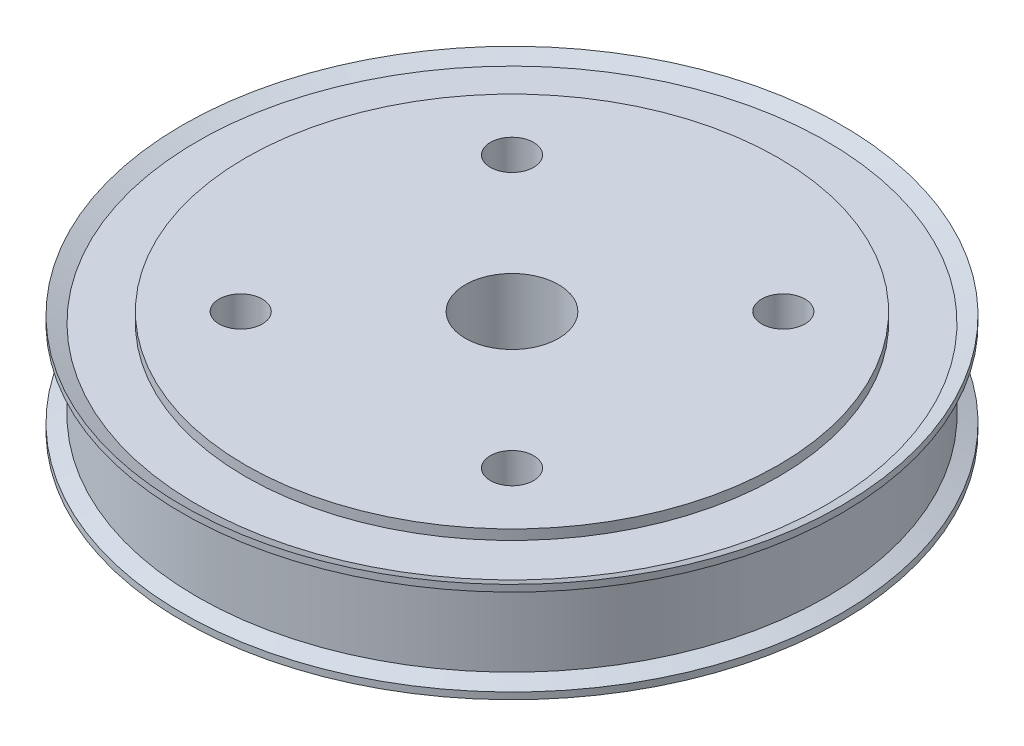
SolidWorks part; units mm, degrees
material "6061 合金"
ref_plane "前基準面" through (0, 0, 0) normal (0, 0, 1) x (1, 0, 0)
ref_plane "上基準面" through (0, 0, 0) normal (0, 1, 0) x (1, 0, 0)
ref_plane "右基準面" through (0, 0, 0) normal (1, 0, 0) x (0, 0, -1)
sketch "草圖1" plane through (0, 0, 0) normal (0, 0, 1) x (1, 0, 0)
  line L0 (0, 49.34) -> (0, -26.8952) construction
  line L1 (47.265, 0) -> (6.3419, 0) construction
  line L3 (7, -8) -> (7, 8)
  line L5 (47.265, 5.5) -> (40, 5.5)
  line L6 (40, 8) -> (40, 5.5)
  line L8 (47.745, 5.5) -> (47.745, -5.5) construction
  line L9 (47.265, -5.5) -> (47.265, 5.5)
  line L10 (40, -5.5) -> (47.265, -5.5)
  line L11 (40, 8) -> (7, 8)
  line L12 (40, -8) -> (40, -5.5)
  line L20 (40, -8) -> (7, -8)
  dimension "D2" = 14
  dimension "D3" = 94.53
  dimension "D6" = 11
  dimension "D7" = 80
  dimension "D8" = 16
  dimension "D9" = 33
  dimension "D12" = 95.49
  dimension "D15" = 7.265
revolve "旋轉1" add sketch "草圖1" angle 360 about L0
sketch "草圖7" plane through (0, 0, 0) normal (0, 0, 1) x (1, 0, 0)
  line L0 (0, 0) -> (0, 8) construction
  line L1 (40, 8) -> (-40, 8) construction
  line L3 (-47.265, -5.5) -> (47.265, -5.5) construction
  line L5 (-40, -5.5) -> (-40, -8) construction
  line L8 (0, 0) -> (-16, 0) construction
  line L12 (-49.5, -6.5) -> (-47.265, -5.5)
  line L13 (-49.5, -7.5) -> (-49.5, -6.5)
  line L14 (-49.5, -7.5) -> (-47.265, -6.5)
  line L15 (-40, -5.5) -> (-40, -6.5)
  line L16 (-47.265, -6.5) -> (-40, -6.5)
  line L17 (-47.265, -5.5) -> (-40, -5.5)
  dimension "D1" = 99
  dimension "D2" = 1
  dimension "D3" = 1
revolve "旋轉2" add sketch "草圖7" angle 360 about L0
mirror "鏡射1" about plane through (0, 0, 0) normal (0, 1, 0) of "旋轉2"
ref_plane "平面1" through (0, 0, 47.265) normal (0, 0, 1) x (1, 0, 0)
ref_axis "基準軸1" through (0, -8, 0) along (0, 1, 0)
hole_wizard "Ø6.5 (6.5) 直徑孔1" positions "草圖10" profile "草圖9" hole size "Ø6.5" standard "JIS" end condition through all
sketch "草圖10" plane through (0, 8, 0) normal (0, 1, 0) x (1, 0, 0)
  line L0 (-17.3345, 0) -> (0, 0) construction
  line L1 (0, 0) -> (-20.375, 20.375) construction
  circle A0 centre (0, 0) radius 28.8146 construction
  point P0 (-20.375, 20.375)
  point P13 (20.375, 20.375)
  point P14 (20.375, -20.375)
  point P15 (-20.375, -20.375)
  point P16 (0, 0)
  dimension "D1" = 40.75
  dimension "D2" = 45
  dimension "D3" = 4
sketch "草圖9" plane through (-20.375, 8, -20.375) normal (1, 0, 0) x (0, 0, 1)
  line L0 (0, 0) -> (0, 16)
  line L1 (0, 16) -> (3.25, 16)
  line L2 (3.25, 16) -> (3.25, 0)
  line L5 (3.25, 0) -> (0, 0)
  line L11 (0, -6.35) -> (0, 107.95) construction
  dimension "貫穿孔直徑" = 6.5
  dimension "貫穿孔深度" = 16
